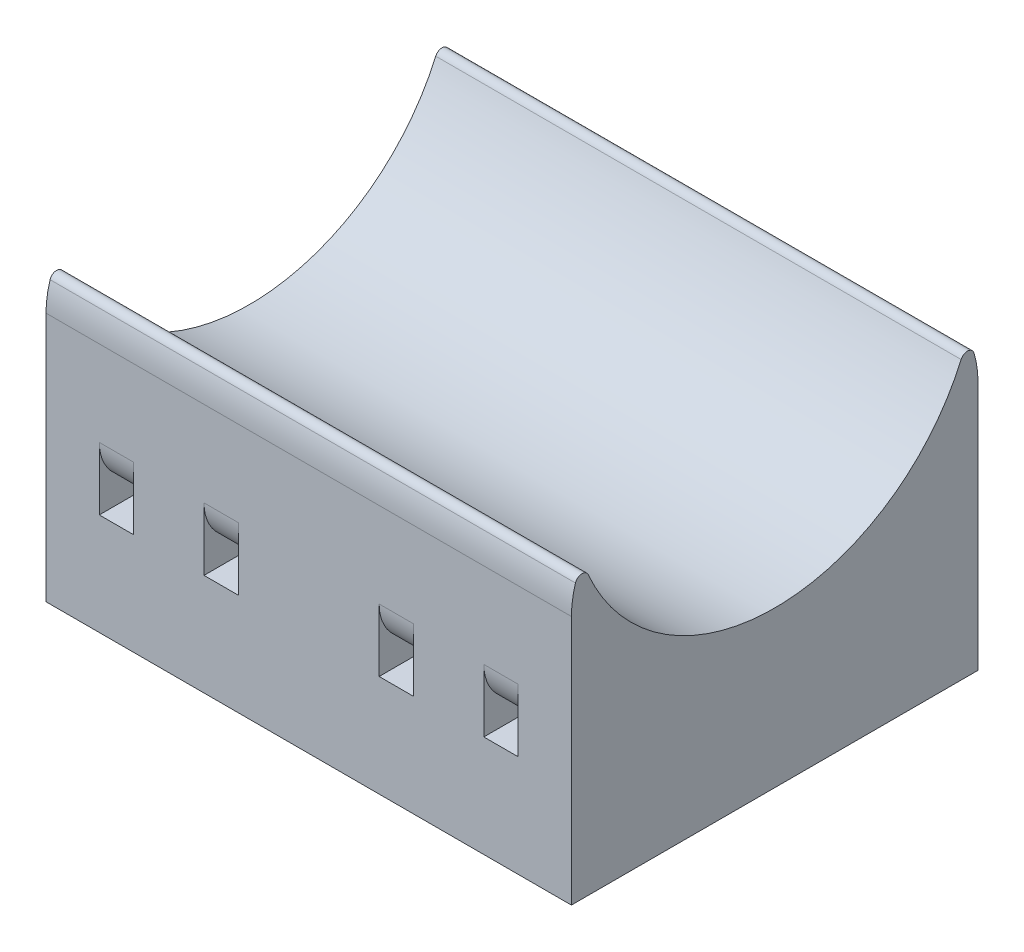
SolidWorks part; units mm, degrees
ref_plane "Front Plane" through (0, 0, 0) normal (0, 0, 1) x (1, 0, 0)
ref_plane "Top Plane" through (0, 0, 0) normal (0, 1, 0) x (1, 0, 0)
ref_plane "Right Plane" through (0, 0, 0) normal (1, 0, 0) x (0, 0, -1)
sketch "Sketch2" plane through (0, 0, 0) normal (0, 1, 0) x (1, 0, 0)
  line L1 (-23, -17.8) -> (23, -17.8)
  line L2 (-23, -17.8) -> (-23, 17.8)
  line L3 (-23, 17.8) -> (23, 17.8)
  line L4 (23, -17.8) -> (23, 17.8)
  line L5 (-23, -17.8) -> (23, 17.8) construction
  line L6 (-23, 17.8) -> (23, -17.8) construction
  point P0 (0, 0)
  dimension "D1" = 46
  dimension "D2" = 35.6
extrude "Boss-Extrude1" add sketch "Sketch2" along normal blind 32
sketch "Sketch3" plane through (23, 0, 0) normal (1, 0, 0) x (0, 0, -1)
  line L0 (-17.8, 25.6678) -> (-16.8494, 25.6678)
  line L1 (0, 32) -> (0, 0) construction
  line L2 (-17.8, 32) -> (17.8, 32) construction
  line L3 (-17.8, 0) -> (17.8, 0) construction
  line L4 (-17.8, 32) -> (-17.8, 0) construction
  line L5 (17.8, 25.6678) -> (16.8494, 25.6678)
  arc A0 (-17.8, 32) -> (17.8, 32) centre (0, 31.4346) ccw
extrude "Cut-Extrude2" cut sketch "Sketch3" against normal up to next
sketch "Sketch4" plane through (0, 0, -17.8) normal (0, 0, -1) x (-1, 0, 0)
  line L0 (0, 25.6678) -> (0, 0) construction
  line L1 (-18.3333, 8.9178) -> (-15.3333, 8.9178)
  line L2 (-18.3333, 8.9178) -> (-18.3333, 10.4178)
  line L3 (-18.3333, 10.4178) -> (-15.3333, 10.4178)
  line L4 (-15.3333, 8.9178) -> (-15.3333, 10.4178)
  line L5 (-18.3333, 8.9178) -> (-15.3333, 10.4178) construction
  line L6 (-18.3333, 10.4178) -> (-15.3333, 8.9178) construction
  line L7 (23, 25.6678) -> (-23, 25.6678) construction
  line L9 (-9.1667, 8.9178) -> (-6.1667, 8.9178)
  line L10 (-9.1667, 8.9178) -> (-9.1667, 10.4178)
  line L11 (-9.1667, 10.4178) -> (-6.1667, 10.4178)
  line L12 (-6.1667, 8.9178) -> (-6.1667, 10.4178)
  line L13 (-9.1667, 8.9178) -> (-6.1667, 10.4178) construction
  line L14 (-9.1667, 10.4178) -> (-6.1667, 8.9178) construction
  line L15 (-23, 25.6678) -> (-23, 0) construction
  line L16 (9.1667, 10.4178) -> (6.1667, 8.9178) construction
  line L17 (9.1667, 8.9178) -> (6.1667, 10.4178) construction
  line L18 (18.3333, 10.4178) -> (15.3333, 8.9178) construction
  line L19 (18.3333, 8.9178) -> (15.3333, 10.4178) construction
  line L20 (6.1667, 8.9178) -> (6.1667, 10.4178)
  line L21 (9.1667, 10.4178) -> (6.1667, 10.4178)
  line L22 (9.1667, 8.9178) -> (9.1667, 10.4178)
  line L23 (9.1667, 8.9178) -> (6.1667, 8.9178)
  line L24 (15.3333, 8.9178) -> (15.3333, 10.4178)
  line L25 (18.3333, 10.4178) -> (15.3333, 10.4178)
  line L26 (18.3333, 8.9178) -> (18.3333, 10.4178)
  line L27 (18.3333, 8.9178) -> (15.3333, 8.9178)
  point P0 (-16.8333, 9.6678)
  point P12 (-7.6667, 9.6678)
  point P14 (-12.0078, 23.5412)
  point P15 (-13.9197, 23.5412)
  point P27 (7.6667, 9.6678)
  point P28 (16.8333, 9.6678)
  dimension "D2" = 16
  dimension "D3" = 3
  dimension "D4" = 1.5
  dimension "D5" = 3
  dimension "D6" = 1.5
  dimension "D8" = 16
  dimension "D1" = 6.1667
  dimension "D7" = 15.3333
extrude "Cut-Extrude3" cut sketch "Sketch4" against normal up to next
fillet "Fillet1" radius 4 8 edges at (7.6667, 10.4178, 17.8) (16.8333, 10.4178, 17.8) (-7.6667, 10.4178, 17.8) (-16.8333, 10.4178, 17.8) (-16.8333, 10.4178, -17.8) (-7.6667, 10.4178, -17.8) (7.6667, 10.4178, -17.8) (16.8333, 10.4178, -17.8)
fillet "Fillet2" radius 8 2 edges at (0, 25.6678, 17.8) (0, 25.6678, -17.8)
fillet "Fillet3" radius 0.6 2 edges at (0, 25.6678, 16.8494) (0, 25.6678, -16.8494)
equation "\"L\" = 46"
equation "\"D1@Sketch2\"=\"L\""
equation "\"W\"= 35.6"
equation "\"D2@Sketch2\"=\"W\""
equation "\"H\"=32"
equation "\"D1@Boss-Extrude1\"=\"H\""
equation "\"D2@Sketch4\"=\"H\"/2"
equation "\"D8@Sketch4\"=\"H\"/2"
equation "\"D1@Sketch4\"=\"L\"/6 - 3/2"
equation "\"D7@Sketch4\"=(\"L\"/6)*2"
